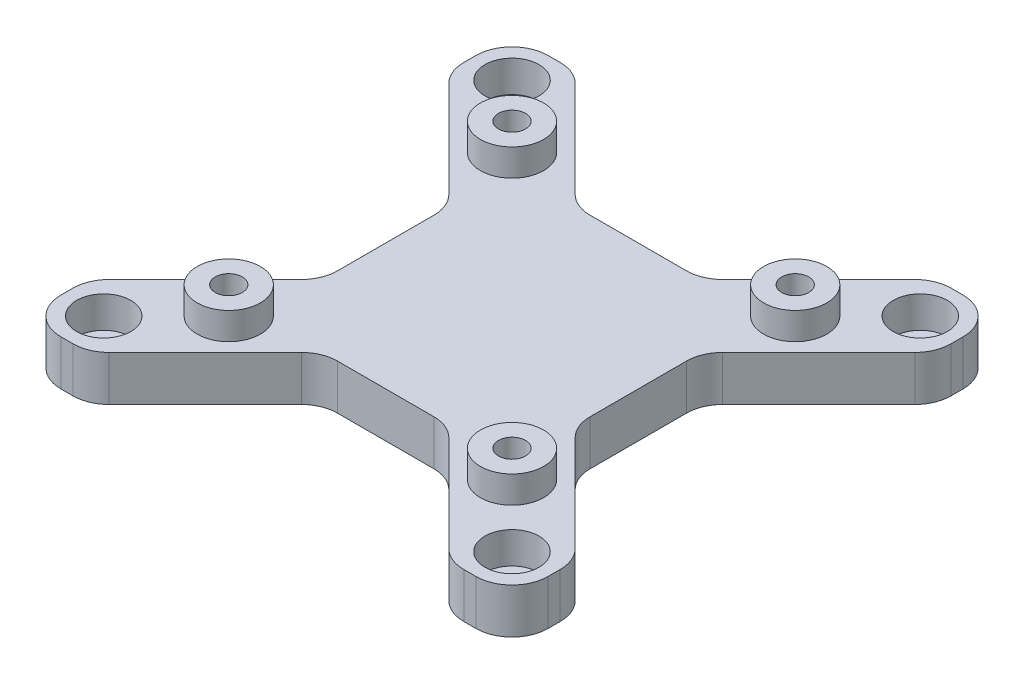
SolidWorks part; units mm, degrees
ref_plane "Płaszczyzna przednia" through (0, 0, 0) normal (0, 0, 1) x (1, 0, 0)
ref_plane "Płaszczyzna górna" through (0, 0, 0) normal (0, 1, 0) x (1, 0, 0)
ref_plane "Płaszczyzna prawa" through (0, 0, 0) normal (1, 0, 0) x (0, 0, -1)
sketch "Szkic2" plane through (0, 0, 0) normal (0, 1, 0) x (1, 0, 0)
  line L0 (-22.625, 22.625) -> (-22.625, -22.625) construction
  line L1 (-22.625, 22.625) -> (22.625, 22.625) construction
  line L2 (22.625, 22.625) -> (22.625, -22.625) construction
  line L3 (22.625, -22.625) -> (-22.625, -22.625) construction
  line L4 (-15.695, 15.695) -> (-15.695, -15.695) construction
  line L5 (-15.695, -15.695) -> (15.695, -15.695) construction
  line L6 (15.695, -15.695) -> (15.695, 15.695) construction
  line L7 (15.695, 15.695) -> (-15.695, 15.695) construction
  line L10 (-22.625, 22.625) -> (22.625, -22.625) construction
  line L12 (-23, -27) -> (23, -27)
  line L13 (-27, -23) -> (-27, 23)
  line L14 (-23, 27) -> (23, 27)
  line L15 (27, -23) -> (27, 23)
  line L16 (-27, -27) -> (27, 27) construction
  line L17 (-27, 27) -> (27, -27) construction
  circle A0 centre (-22.625, 22.625) radius 1.7
  circle A1 centre (22.625, 22.625) radius 1.7
  circle A2 centre (22.625, -22.625) radius 1.7
  circle A3 centre (-22.625, -22.625) radius 1.7
  circle A4 centre (15.695, 15.695) radius 1.5
  circle A5 centre (-15.695, 15.695) radius 1.5
  circle A6 centre (-15.695, -15.695) radius 1.5
  circle A7 centre (15.695, -15.695) radius 1.5
  circle A8 centre (-15.695, 15.695) radius 3.5
  circle A9 centre (15.695, 15.695) radius 3.5
  circle A10 centre (-15.695, -15.695) radius 3.5
  circle A11 centre (15.695, -15.695) radius 3.5
  arc A12 (-23, 27) -> (-27, 23) centre (-23, 23) ccw
  arc A13 (27, 23) -> (23, 27) centre (23, 23) ccw
  arc A14 (27, -23) -> (23, -27) centre (23, -23) cw
  arc A15 (-23, -27) -> (-27, -23) centre (-23, -23) cw
  point P9 (0, 0)
  point P21 (0, 0)
  point P22 (0, 0)
  point P24 (0, 0)
  dimension "D1" = 4
  dimension "D2" = 4
  dimension "D3" = 4
  dimension "D4" = 4
  dimension "D5" = 7
  dimension "D6" = 7
  dimension "D7" = 7
  dimension "D8" = 7
  dimension "D9" = 3
  dimension "D10" = 3
  dimension "D11" = 3
  dimension "D12" = 3
  dimension "D19" = 3.4
  dimension "D20" = 3.4
  dimension "D21" = 3.4
  dimension "D22" = 3.4
  dimension "D13" = 31.39
  dimension "D14" = 31.39
  dimension "D15" = 45.25
  dimension "D16" = 45.25
  dimension "D17" = 54
  dimension "D18" = 54
extrude "Dodanie-wyciągnięcie1" add sketch "Szkic2" against normal blind 5 contours A15 L12 A14 L15 A13 L14 A12 L13 A11 A10 A9 A8 A3 A2 A1 A0 | A9 A4 | A8 A5 | A11 A7 | A10 A6 region at (0, 0, 0) region at (-19.096, 0, -15.695) region at (12.294, 0, -15.695) region at (-19.096, 0, 15.695) region at (12.294, 0, 15.695)
extrude "Dodanie-wyciągnięcie2" add sketch "Szkic2<3>" along normal blind 3 contours A7 | A6 | A5 | A4 | A11 | A10 | A8 | A9 region at (15.695, 0, -15.695) region at (-15.695, 0, -15.695) region at (-15.695, 0, 15.695) region at (15.695, 0, 15.695)
sketch "Szkic2<3>" plane through (0, 0, 0) normal (0, 1, 0) x (1, 0, 0) same geometry as "Szkic2"
sketch "Szkic3" plane through (0, 0, 0) normal (0, 1, 0) x (1, 0, 0)
  line L0 (0, -27) -> (0, -14) construction
  line L1 (-23, -27) -> (23, -27) construction
  line L2 (-7, -14) -> (7, -14)
  line L3 (-20, -27) -> (20, -27)
  line L4 (7, -14) -> (20, -27)
  line L5 (-7, -14) -> (-20, -27)
  point P7 (0, -14)
  point P10 (0, -27)
  dimension "D1" = 14
  dimension "D2" = 45
  dimension "D3" = 13
extrude "Wytnij-wyciągnięcie1" cut sketch "Szkic3" against normal through all
ref_axis "Oś1" through (0, -8.6, 0) along (0, 1, 0)
pattern_circular "Szyk kołowy1" count 4 every 90 about axis through (0, -8.6, 0) along (0, 1, 0) of "Wytnij-wyciągnięcie1"
fillet "Zaokrąglenie1" radius 4 16 edges at (20, -2.5, 27) (7, -2.5, 14) (-20, -2.5, 27) (-7, -2.5, 14) (27, -2.5, -20) (14, -2.5, -7) (14, -2.5, 7) (27, -2.5, 20) (20, -2.5, -27) (7, -2.5, -14) (-20, -2.5, -27) (-7, -2.5, -14) (-27, -2.5, 20) (-14, -2.5, 7) (-14, -2.5, -7) (-27, -2.5, -20)
sketch "Szkic5" plane through (0, 0, 0) normal (0, 1, 0) x (1, 0, 0)
  circle A0 centre (-22.625, -22.625) radius 3
  circle A1 centre (-22.625, 22.625) radius 3
  circle A2 centre (22.625, 22.625) radius 3
  circle A3 centre (22.625, -22.625) radius 3
  dimension "D1" = 6
  dimension "D2" = 6
  dimension "D3" = 6
  dimension "D4" = 6
extrude "Wytnij-wyciągnięcie3" cut sketch "Szkic5" against normal blind 3.5
sketch "Szkic4" plane through (0, 3, 0) normal (0, 1, 0) x (1, 0, 0)
  circle A0 centre (-15.695, 15.695) radius 2.25
  circle A1 centre (15.695, 15.695) radius 2.25
  circle A2 centre (15.695, -15.695) radius 2.25
  circle A3 centre (-15.695, -15.695) radius 2.25
  dimension "D1" = 4.5
  dimension "D2" = 4.5
  dimension "D3" = 4.5
  dimension "D4" = 4.5
equation "\"M3_insert\"=4.5"
equation "\"D2@Szkic4\"=\"M3_insert\""
equation "\"D1@Szkic4\"=\"M3_insert\""
equation "\"D3@Szkic4\"=\"M3_insert\""
equation "\"D4@Szkic4\"=\"M3_insert\""
equation "\"M3_screw\"=6"
equation "\"D1@Szkic5\"=\"M3_screw\""
equation "\"D2@Szkic5\"=\"M3_screw\""
equation "\"D3@Szkic5\"=\"M3_screw\""
equation "\"D4@Szkic5\"=\"M3_screw\""
